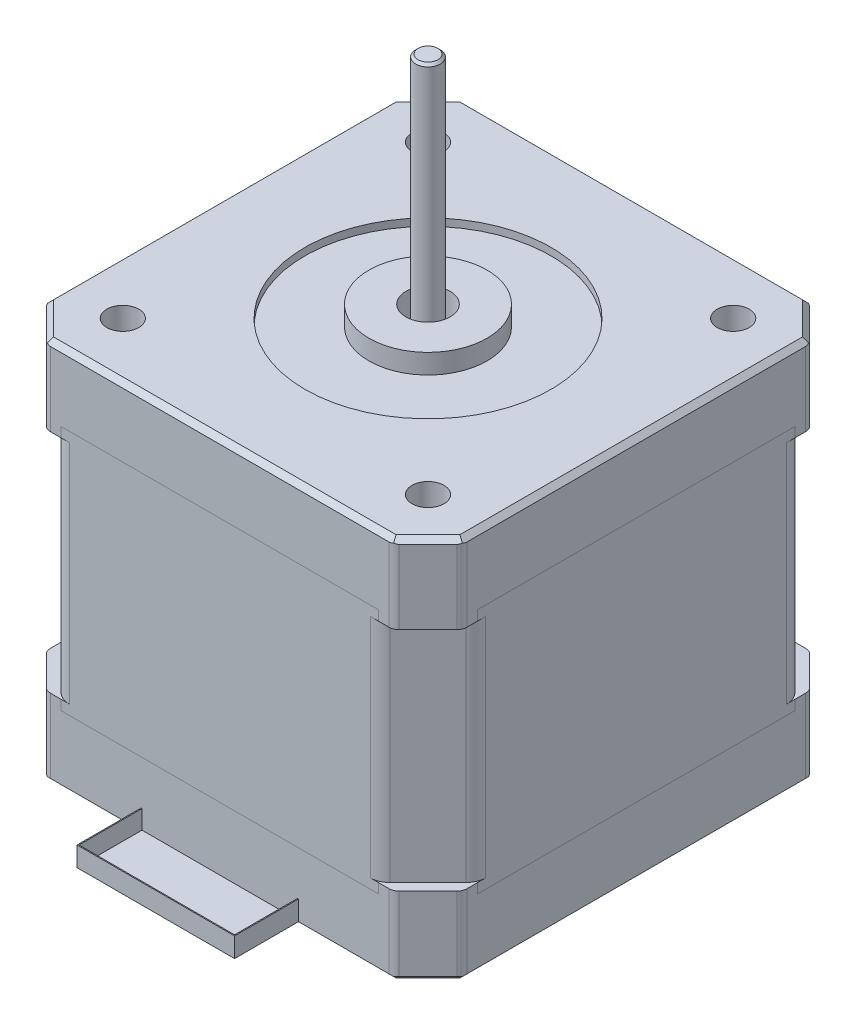
SolidWorks part; units mm, degrees
ref_plane "Front Plane" through (0, 0, 0) normal (0, 0, 1) x (1, 0, 0)
ref_plane "Top Plane" through (0, 0, 0) normal (0, 1, 0) x (1, 0, 0)
ref_plane "Right Plane" through (0, 0, 0) normal (1, 0, 0) x (0, 0, -1)
sketch "Sketch1" plane through (0, 0, 0) normal (0, 1, 0) x (1, 0, 0)
  line L0 (-41.2413, 0) -> (21.15, 0) construction
  line L1 (0, -27.9894) -> (0, 21.15) construction
  line L2 (-21.15, -17.6145) -> (-21.15, 17.6145)
  line L3 (-21.15, 17.6145) -> (-17.6145, 21.15)
  line L4 (-17.6145, 21.15) -> (17.6145, 21.15)
  line L5 (17.6145, 21.15) -> (21.15, 17.6145)
  line L6 (21.15, 17.6145) -> (21.15, -17.6145)
  line L7 (21.15, -17.6145) -> (17.6145, -21.15)
  line L8 (17.6145, -21.15) -> (-17.6145, -21.15)
  line L9 (-17.6145, -21.15) -> (-21.15, -17.6145)
  dimension "D1" = 42.3
  dimension "D2" = 45
  dimension "D3" = 5
extrude "Boss-Extrude1" add sketch "Sketch1" against normal blind 8
sketch "Sketch2" plane through (0, 0, 0) normal (0, 1, 0) x (1, 0, 0)
  line L0 (-21.15, 0) -> (21.15, 0) construction
  line L1 (-21.15, 17.6145) -> (-21.15, -17.6145) construction
  line L2 (21.15, -17.6145) -> (21.15, 17.6145) construction
  line L3 (0, -21.15) -> (0, 21.15) construction
  line L4 (-17.6145, -21.15) -> (17.6145, -21.15) construction
  line L5 (17.6145, 21.15) -> (-17.6145, 21.15) construction
  circle A0 centre (-15.5, 15.5) radius 1.6248
  circle A1 centre (15.5, 15.5) radius 1.6248
  circle A2 centre (15.5, -15.5) radius 1.6248
  circle A3 centre (-15.5, -15.5) radius 1.6248
  dimension "D1" = 31
  dimension "D2" = 31
extrude "Cut-Extrude1" cut sketch "Sketch2" against normal blind 6
chamfer "Chamfer1" distance 0.5 angle 45 8 edges at (-21.15, 0, 0) (-19.3822, 0, -19.3822) (0, 0, -21.15) (19.3822, 0, -19.3822) (21.15, 0, 0) (19.3822, 0, 19.3822) (0, 0, 21.15) (-19.3822, 0, 19.3822)
sketch "Sketch3" plane through (21.15, 0, 0) normal (1, 0, 0) x (0, 0, -1)
  line L0 (-16.1145, -8) -> (16.1145, -8)
  line L1 (-17.6145, -8) -> (17.6145, -8) construction
  line L2 (-16.1145, -8) -> (-16.1145, -7)
  line L3 (-16.1145, -7) -> (16.1145, -7)
  line L4 (16.1145, -7) -> (16.1145, -8)
  dimension "D1" = 1.5
  dimension "D2" = 1.5
  dimension "D3" = 1
extrude "Cut-Extrude2" cut sketch "Sketch3" against normal through all
sketch "Sketch4" plane through (0, 0, 21.15) normal (0, 0, 1) x (1, 0, 0)
  line L0 (-16.1145, -8) -> (-16.1145, -7)
  line L1 (-17.6145, -8) -> (17.6145, -8) construction
  line L2 (-16.1145, -7) -> (16.1145, -7)
  line L3 (16.1145, -7) -> (16.1145, -8)
  line L4 (16.1145, -8) -> (-16.1145, -8)
  line L5 (-17.6145, -8) -> (-17.6145, -0.5) construction
  line L6 (17.6145, -8) -> (17.6145, -0.5) construction
  dimension "D1" = 1.5
  dimension "D2" = 1.5
  dimension "D3" = 1
extrude "Cut-Extrude3" cut sketch "Sketch4" against normal through all
sketch "Sketch5" plane through (0, -8, 0) normal (0, -1, 0) x (1, 0, 0)
  line L0 (-21.15, 16.1145) -> (-16.1145, 21.15)
  line L4 (-21.15, 16.1145) -> (-16.1145, 16.1145)
  line L5 (-16.1145, 16.1145) -> (-16.1145, 21.15)
extrude "Cut-Extrude4" cut sketch "Sketch5" against normal blind 1
mirror "Mirror1" about plane through (0, 0, 0) normal (1, 0, 0) of "Cut-Extrude4"
mirror "Mirror2" about plane through (0, 0, 0) normal (0, 0, 1) of "Mirror1"
sketch "Sketch6" plane through (0, -7, 0) normal (0, -1, 0) x (1, 0, 0)
  line L0 (-21.15, -16.1145) -> (-21.15, 16.1145)
  line L1 (-21.15, 16.1145) -> (-16.1145, 21.15)
  line L2 (-16.1145, 21.15) -> (16.1145, 21.15)
  line L3 (16.1145, 21.15) -> (21.15, 16.1145)
  line L4 (21.15, 16.1145) -> (21.15, -16.1145)
  line L5 (21.15, -16.1145) -> (16.1145, -21.15)
  line L6 (16.1145, -21.15) -> (-16.1145, -21.15)
  line L7 (-16.1145, -21.15) -> (-21.15, -16.1145)
extrude "Boss-Extrude2" add sketch "Sketch6" along normal blind 24
sketch "Sketch12" plane through (21.15, 0, 0) normal (1, 0, 0) x (0, 0, -1)
  line L0 (-16.1145, -8) -> (-16.1145, -7)
  line L1 (-16.1145, -7) -> (16.1145, -7)
  line L2 (16.1145, -7) -> (16.1145, -8)
  dimension "D1" = 1
split line "Split Line5"
sketch "Sketch13" plane through (0, 0, -21.15) normal (0, 0, -1) x (-1, 0, 0)
  line L0 (-16.1145, -8) -> (-16.1145, -7)
  line L1 (-16.1145, -7) -> (16.1145, -7)
  line L2 (16.1145, -7) -> (16.1145, -8)
  dimension "D1" = 1
split line "Split Line6"
sketch "Sketch14" plane through (-21.15, 0, 0) normal (-1, 0, 0) x (0, 0, 1)
  line L0 (-16.1145, -8) -> (-16.1145, -7)
  line L1 (-16.1145, -7) -> (16.1145, -7)
  line L2 (16.1145, -7) -> (16.1145, -8)
  dimension "D1" = 1
split line "Split Line7"
sketch "Sketch15" plane through (0, 0, 21.15) normal (0, 0, 1) x (1, 0, 0)
  line L0 (-16.1145, -8) -> (-16.1145, -7)
  line L1 (-16.1145, -7) -> (16.1145, -7)
  line L2 (16.1145, -7) -> (16.1145, -8)
  dimension "D1" = 1
split line "Split Line8"
sketch "Sketch16" plane through (0, -31, 0) normal (0, -1, 0) x (1, 0, 0)
  line L0 (-21.15, -17.6145) -> (-21.15, 17.6145)
  line L1 (-21.15, 17.6145) -> (-17.6145, 21.15)
  line L2 (-17.6145, 21.15) -> (17.6145, 21.15)
  line L3 (17.6145, 21.15) -> (21.15, 17.6145)
  line L4 (21.15, 17.6145) -> (21.15, -17.6145)
  line L5 (21.15, -17.6145) -> (17.6145, -21.15)
  line L6 (17.6145, -21.15) -> (-17.6145, -21.15)
  line L7 (-17.6145, -21.15) -> (-21.15, -17.6145)
extrude "Boss-Extrude4" add sketch "Sketch16" along normal blind 8
sketch "Sketch17" plane through (0, 0, 21.15) normal (0, 0, 1) x (1, 0, 0)
  line L0 (-16.1145, -31) -> (-16.1145, -32)
  line L1 (-16.1145, -32) -> (16.1145, -32)
  line L2 (16.1145, -32) -> (16.1145, -31)
  dimension "D1" = 1
split line "Split Line9"
sketch "Sketch18" plane through (21.15, 0, 0) normal (1, 0, 0) x (0, 0, -1)
  line L0 (-16.1145, -31) -> (-16.1145, -32)
  line L1 (-16.1145, -32) -> (16.1145, -32)
  line L2 (16.1145, -32) -> (16.1145, -31)
  dimension "D1" = 1
split line "Split Line10"
sketch "Sketch19" plane through (0, 0, -21.15) normal (0, 0, -1) x (-1, 0, 0)
  line L0 (-16.1145, -31) -> (-16.1145, -32)
  line L1 (-16.1145, -32) -> (16.1145, -32)
  line L2 (16.1145, -32) -> (16.1145, -31)
  dimension "D1" = 1
split line "Split Line11"
sketch "Sketch20" plane through (-21.15, 0, 0) normal (-1, 0, 0) x (0, 0, 1)
  line L0 (-16.1145, -31) -> (-16.1145, -32)
  line L1 (-16.1145, -32) -> (16.1145, -32)
  line L2 (16.1145, -32) -> (16.1145, -31)
  dimension "D1" = 1
split line "Split Line12"
sketch "Sketch22" plane through (0, 0, 21.15) normal (0, 0, 1) x (1, 0, 0)
  line L0 (-8, -39) -> (8, -39)
  line L1 (17.6145, -39) -> (-17.6145, -39) construction
  line L2 (8, -39) -> (8, -36.5)
  line L3 (8, -36.5) -> (-8, -36.5)
  line L4 (-8, -36.5) -> (-8, -39)
  line L5 (0, 0) -> (0, -39) construction
  dimension "D1" = 16
  dimension "D2" = 2.5
extrude "Boss-Extrude5" add sketch "Sketch22" along normal blind 6.5
chamfer "Chamfer3" distance 0.5 angle 45 12 edges at (-21.15, -39, 0) (-19.3822, -39, 19.3822) (-12.8072, -39, 21.15) (-8, -39, 24.4) (0, -39, 27.65) (8, -39, 24.4) (12.8072, -39, 21.15) (19.3822, -39, 19.3822) (21.15, -39, 0) (19.3822, -39, -19.3822) (0, -39, -21.15) (-19.3822, -39, -19.3822)
sketch "Sketch23" plane through (0, -36.5, 0) normal (0, 1, 0) x (1, 0, 0)
  line L0 (-8, -27.65) -> (-8, -21.15) construction
  line L1 (-7.9, -21.15) -> (7.9, -21.15)
  line L2 (-7.9, -21.15) -> (-7.9, -27.55)
  line L3 (-7.9, -27.55) -> (7.9, -27.55)
  line L4 (7.9, -21.15) -> (7.9, -27.55)
  line L5 (-7.9, -21.15) -> (7.9, -27.55) construction
  line L6 (-7.9, -27.55) -> (7.9, -21.15) construction
  line L7 (8, -27.65) -> (8, -21.15) construction
  line L8 (8, -27.65) -> (-8, -27.65) construction
  line L10 (8, -21.15) -> (-8, -21.15) construction
  point P0 (0, -24.35)
  dimension "D1" = 0.1
  dimension "D2" = 0.1
  dimension "D3" = 0.1
extrude "Cut-Extrude5" cut sketch "Sketch23" against normal blind 1.9
sketch "Sketch24" plane through (0, 0, 0) normal (0, 1, 0) x (1, 0, 0)
  circle A0 centre (0, 0) radius 12.5
  dimension "D1" = 25
extrude "Cut-Extrude6" cut sketch "Sketch24" against normal blind 0.75
sketch "Sketch25" plane through (0, -0.75, 0) normal (0, 1, 0) x (1, 0, 0)
  circle A0 centre (0, 0) radius 6
  dimension "D1" = 12
extrude "Boss-Extrude6" add sketch "Sketch25" along normal blind 2
sketch "Sketch26" plane through (0, 1.25, 0) normal (0, 1, 0) x (1, 0, 0)
  circle A0 centre (0, 0) radius 2.25
  dimension "D1" = 4.5
extrude "Cut-Extrude7" cut sketch "Sketch26" against normal blind 5
sketch "Sketch27" plane through (0, -3.75, 0) normal (0, 1, 0) x (1, 0, 0)
  circle A0 centre (0, 0) radius 1.2521
  dimension "D1" = 2.5041
extrude "Boss-Extrude7" add sketch "Sketch27" along normal blind 27
chamfer "Chamfer5" distance 0.25 angle 45 1 edges at (0, 23.25, 1.2521)
fillet "Fillet1" radius 2 8 edges at (-16.1145, -19.5, 21.15) (-21.15, -19.5, 16.1145) (-21.15, -19.5, -16.1145) (-16.1145, -19.5, -21.15) (21.15, -19.5, -16.1145) (16.1145, -19.5, -21.15) (21.15, -19.5, 16.1145) (16.1145, -19.5, 21.15)
fillet "Fillet3" radius 1 8 edges at (-17.6145, -4.25, 21.15) (-21.15, -4.25, 17.6145) (-21.15, -4.25, -17.6145) (-17.6145, -4.25, -21.15) (17.6145, -4.25, -21.15) (21.15, -4.25, -17.6145) (17.6145, -4.25, 21.15) (21.15, -4.25, 17.6145)
fillet "Fillet4" radius 1 8 edges at (-17.6145, -34.75, 21.15) (-21.15, -34.75, 17.6145) (-21.15, -34.75, -17.6145) (-17.6145, -34.75, -21.15) (17.6145, -34.75, -21.15) (21.15, -34.75, -17.6145) (21.15, -34.75, 17.6145) (17.6145, -34.75, 21.15)
